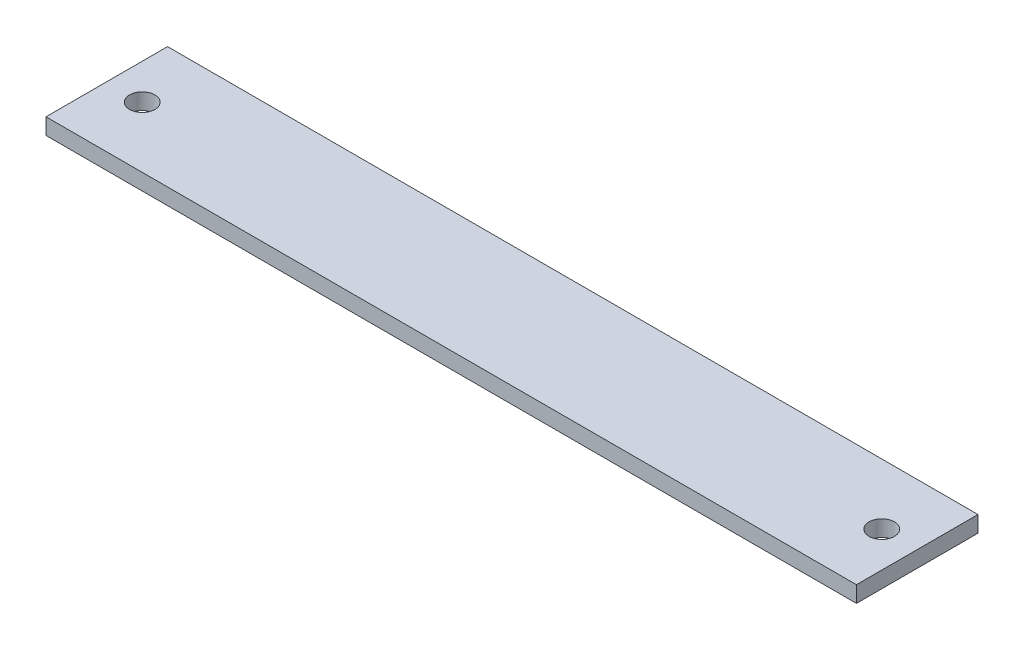
SolidWorks part; units mm, degrees
ref_plane "Front Plane" through (0, 0, 0) normal (0, 0, 1) x (1, 0, 0)
ref_plane "Top Plane" through (0, 0, 0) normal (0, 1, 0) x (1, 0, 0)
ref_plane "Right Plane" through (0, 0, 0) normal (1, 0, 0) x (0, 0, -1)
sketch "Sketch1" plane through (0, 0, 0) normal (0, 1, 0) x (1, 0, 0)
  line L1 (0, 0) -> (-80, 0)
  line L2 (0, 0) -> (0, 12)
  line L3 (0, 12) -> (-80, 12)
  line L4 (-80, 0) -> (-80, 12)
  dimension "D1" = 12
  dimension "D2" = 80
extrude "pcb" add sketch "Sketch1" along normal blind 1.6
sketch "Sketch2" plane through (0, 1.6, 0) normal (0, 1, 0) x (1, 0, 0)
  line L0 (-80, 12) -> (-80, 0) construction
  line L1 (0, 0) -> (0, 12) construction
  circle A0 centre (-76.5, 6) radius 1.25
  circle A1 centre (-3.5, 6) radius 1.25
  dimension "D3" = 2.5
  dimension "D4" = 2.5
  dimension "D1" = 3.5
  dimension "D2" = 3.5
extrude "screw holes" cut sketch "Sketch2" against normal through all
